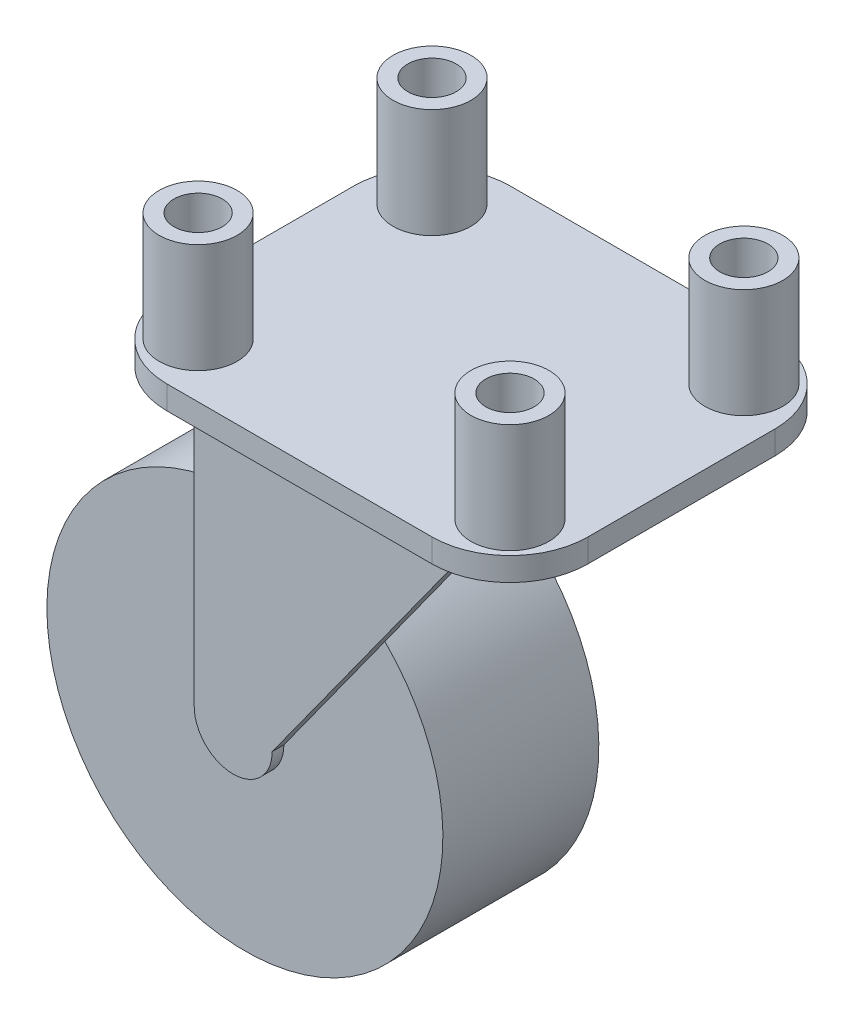
SolidWorks part; units mm, degrees
ref_plane "前视基准面" through (0, 0, 0) normal (0, 0, 1) x (1, 0, 0)
ref_plane "上视基准面" through (0, 0, 0) normal (0, 1, 0) x (1, 0, 0)
ref_plane "右视基准面" through (0, 0, 0) normal (1, 0, 0) x (0, 0, -1)
sketch "草图1" plane through (0, 0, 0) normal (0, 0, 1) x (1, 0, 0)
  circle A0 centre (0, 0) radius 25.4
  dimension "D1" = 50.8
extrude "凸台-拉伸1" add sketch "草图1" along normal blind 10 and the other way blind 10
sketch "草图2" plane through (0, 0, 10) normal (0, 0, 1) x (1, 0, 0)
  line L0 (-5, 0) -> (-5, 41.6)
  line L1 (-5, 41.6) -> (35, 41.6)
  line L2 (15, 41.6) -> (15, 28.049) construction
  line L3 (35, 41.6) -> (5, 0)
  arc A0 (-5, 0) -> (5, 0) centre (0, 0) ccw
  dimension "D1" = 10
  dimension "D2" = 41.6
  dimension "D3" = 40
extrude "凸台-拉伸2" add sketch "草图2" along normal blind 1.5
mirror "镜向1" about plane through (0, 0, 0) normal (0, 0, 1) of "凸台-拉伸2"
sketch "草图3" plane through (0, 41.6, 0) normal (0, 1, 0) x (1, 0, 0)
  line L0 (19, -22) -> (19, 22) construction
  line L1 (-8, 22) -> (46, 22)
  line L2 (-8, 22) -> (-8, -22)
  line L3 (-8, -22) -> (46, -22)
  line L4 (46, 22) -> (46, -22)
  dimension "D1" = 54
  dimension "D2" = 44
  dimension "D3" = 22
  dimension "D4" = 19
extrude "凸台-拉伸3" add sketch "草图3" along normal blind 3
sketch "草图4" plane through (0, 44.6, 0) normal (0, 1, 0) x (1, 0, 0)
  line L0 (19, 22) -> (19, -22) construction
  line L1 (46, 22) -> (-8, 22) construction
  line L2 (-8, -22) -> (46, -22) construction
  line L3 (-8, 0) -> (46, 0) construction
  line L4 (-8, 22) -> (-8, -22) construction
  line L5 (46, -22) -> (46, 22) construction
  circle A0 centre (-1, 15) radius 3.1
  circle A1 centre (39, 15) radius 3.1
  circle A2 centre (39, -15) radius 3.1
  circle A3 centre (-1, -15) radius 3.1
  dimension "D1" = 20
  dimension "D2" = 20
  dimension "D3" = 6.2
  dimension "D4" = 6.2
  dimension "D5" = 15
  dimension "D6" = 15
extrude "切除-拉伸1" cut sketch "草图4" along direction (0, 1, 0) on the side against the normal up to next (3 mm away)
fillet "圆角1" radius 10 4 edges at (46, 43.1, -22) (46, 43.1, 22) (-8, 43.1, 22) (-8, 43.1, -22)
sketch "草图5" plane through (0, 44.6, 0) normal (0, 1, 0) x (1, 0, 0)
  circle A0 centre (-1, 15) radius 3.1
  circle A1 centre (-1, 15) radius 5
  circle A3 centre (39, 15) radius 3.1
  circle A4 centre (39, 15) radius 5
  circle A5 centre (-1, -15) radius 3.1
  circle A6 centre (-1, -15) radius 5
  circle A7 centre (39, -15) radius 3.1
  circle A8 centre (39, -15) radius 5
  dimension "D1" = 10
  dimension "D2" = 10
  dimension "D3" = 10
  dimension "D4" = 10
extrude "凸台-拉伸4" add sketch "草图5" along normal blind 14
